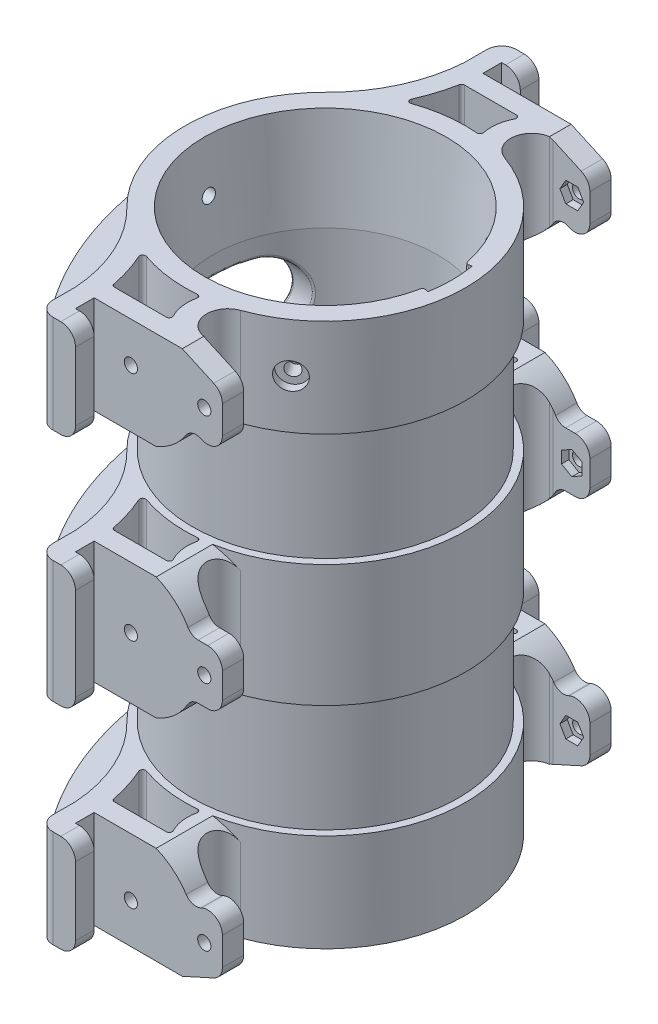
SolidWorks part; units mm, degrees
ref_plane "Front Plane" through (0, 0, 0) normal (0, 0, 1) x (1, 0, 0)
ref_plane "Top Plane" through (0, 0, 0) normal (0, 1, 0) x (1, 0, 0)
ref_plane "Right Plane" through (0, 0, 0) normal (1, 0, 0) x (0, 0, -1)
sketch "Sketch1" plane through (0, 0, 0) normal (0, 1, 0) x (1, 0, 0)
  line L0 (0, 38.25) -> (0, 45.25) construction
  circle A0 centre (0, 0) radius 38.25
  circle A1 centre (0, 0) radius 45.25
  dimension "D1" = 76.5
  dimension "D2" = 7
extrude "Boss-Extrude1" add sketch "Sketch1" along normal mid plane 185
sketch "Sketch2" plane through (0, -92.5, 0) normal (0, -1, 0) x (1, 0, 0)
  line L0 (0, 36.25) -> (0, 38.25) construction
  circle A0 centre (0, 0) radius 36.25
  circle A1 centre (0, 0) radius 38.25 construction
  circle A2 centre (0, 0) radius 38.25
  dimension "D1" = 2
extrude "Boss-Extrude2" add sketch "Sketch2" against normal blind 100 from offset 6.35 offset against normal yes
sketch "Sketch7" plane through (0, 0, 0) normal (1, 0, 0) x (0, 0, -1)
  line L0 (45.25, 92.5) -> (-45.25, 92.5) construction
  line L1 (12.5, 40) -> (-12.5, 40) construction
  line L2 (12.5, 27.5) -> (-12.5, 27.5)
  line L3 (12.5, 52.5) -> (-12.5, 52.5)
  circle A0 centre (0, 40) radius 12.5 construction
  arc A1 (12.5, 27.5) -> (12.5, 52.5) centre (12.5, 40) ccw
  arc A2 (-12.5, 52.5) -> (-12.5, 27.5) centre (-12.5, 40) ccw
  point P7 (0, 40)
  dimension "D2" = 25
  dimension "D3" = 25
  dimension "D1" = 52.5
extrude "Cut-Extrude4" cut sketch "Sketch7" against normal through all
sketch "Sketch8" plane through (0, 0, 0) normal (0, 1, 0) x (1, 0, 0)
  line L1 (17.5, -66.175) -> (128.1882, -66.175) construction
  line L2 (-18.85, -66.175) -> (-18.85, -78.875)
  line L3 (-18.85, -78.875) -> (-6.15, -78.875)
  line L4 (45.25, 0) -> (-45.25, 0) construction
  line L5 (31.75, 0) -> (50, 0) construction
  line L6 (-6.15, -78.875) -> (-6.15, -72.525)
  line L7 (-12.5, -72.525) -> (17.5, -72.525) construction
  line L8 (-6.15, -72.525) -> (-12.5, -72.525)
  line L9 (-12.5, -72.525) -> (-12.5, -66.175)
  line L10 (-12.5, -66.175) -> (43.65, -66.175)
  line L11 (-12.5, 66.175) -> (43.65, 66.175)
  line L12 (-12.5, 72.525) -> (-12.5, 66.175)
  line L13 (-6.15, 72.525) -> (-12.5, 72.525)
  line L14 (-6.15, 78.875) -> (-6.15, 72.525)
  line L15 (-18.85, 78.875) -> (-6.15, 78.875)
  line L16 (-18.85, 66.175) -> (-18.85, 78.875)
  line L18 (43.65, -66.175) -> (43.65, -58.9107)
  line L19 (43.65, -58.9107) -> (18.65, -58.9107)
  line L20 (43.65, 58.9107) -> (18.65, 58.9107)
  line L21 (43.65, 66.175) -> (43.65, 58.9107)
  line L22 (-12.5, -72.525) -> (-18.85, -72.525) construction
  arc A0 (-32.8241, -31.1471) -> (-18.85, -66.175) centre (-69.7381, -66.175) cw
  circle A1 centre (0, 0) radius 45.25 construction
  arc A2 (-32.8241, -31.1471) -> (15.7007, -42.4388) centre (0, 0) ccw
  arc A3 (-32.8241, 31.1471) -> (15.7007, 42.4388) centre (0, 0) cw
  arc A4 (-32.8241, 31.1471) -> (-18.85, 66.175) centre (-69.7381, 66.175) ccw
  arc A9 (18.65, -58.9107) -> (15.7007, -42.4388) centre (18.65, -50.4107) cw
  arc A10 (18.65, 58.9107) -> (15.7007, 42.4388) centre (18.65, 50.4107) ccw
  dimension "D1" = 8.5
  dimension "D2" = 62.5
  dimension "D3" = 25
extrude "Boss-Extrude3" add sketch "Sketch8" along normal up to surface and the other way up to surface up to face at (0, 92.5, 45.25) other way up to face at (0, -92.5, 45.25)
sketch "Sketch10" plane through (0, 0, 66.175) normal (0, 0, 1) x (1, 0, 0)
  line L0 (17.5, -92.5) -> (43.65, -92.5)
  line L1 (43.65, -92.5) -> (43.65, -80.6536)
  line L2 (-6.15, -59.2129) -> (-32.8241, -59.2129)
  line L3 (128.1882, -42.3564) -> (17.5, -92.5) construction
  line L4 (43.65, -80.6536) -> (17.5, -92.5)
  line L5 (43.65, 80.6536) -> (43.65, 92.5)
  line L6 (17.5, 92.5) -> (128.1882, 42.3564) construction
  line L7 (43.65, 92.5) -> (17.5, 92.5)
  line L8 (-12.5, 92.5) -> (43.65, 92.5) construction
  line L9 (17.5, 92.5) -> (43.65, 80.6536)
  line L10 (43.65, -60.1882) -> (43.65, -9.3209)
  line L11 (79.953, -43.7423) -> (23.8431, -69.161) construction
  line L12 (22.9086, -9.3209) -> (60.2886, -9.3209) construction
  line L21 (22.9086, -9.3209) -> (43.65, -9.3209)
  line L23 (43.65, -60.1882) -> (23.8431, -69.161)
  line L25 (-6.15, 92.5) -> (-6.15, -92.5) construction
  line L26 (-32.8241, 92.5) -> (-32.8241, -92.5) construction
  line L32 (-32.8241, -59.2129) -> (-32.8241, -20.7871)
  line L36 (-32.8241, -20.7871) -> (-6.15, -20.7871)
  line L40 (0, 0) -> (-32.8241, 0) construction
  line L45 (8.611, -59.2129) -> (-6.15, -59.2129)
  line L46 (8.611, -20.7871) -> (-6.15, -20.7871)
  line L47 (-32.8241, 59.2129) -> (-32.8241, 20.7871)
  line L48 (-6.15, 59.2129) -> (-32.8241, 59.2129)
  line L49 (8.611, 59.2129) -> (-6.15, 59.2129)
  line L50 (43.65, 60.1882) -> (23.8431, 69.161)
  line L51 (43.65, 60.1882) -> (43.65, 9.3209)
  line L52 (22.9086, 9.3209) -> (43.65, 9.3209)
  line L53 (8.611, 20.7871) -> (-6.15, 20.7871)
  line L54 (-32.8241, 20.7871) -> (-6.15, 20.7871)
  line L55 (43.65, 92.5) -> (43.65, -92.5) construction
  arc A6 (18.8427, -67.7035) -> (23.8431, -69.161) centre (22.1925, -65.5175) ccw construction
  arc A7 (18.8427, -67.7035) -> (8.611, -59.2129) centre (0, -80) ccw construction
  arc A10 (8.611, -20.7871) -> (19.4507, -11.3102) centre (0, 0) ccw construction
  arc A11 (22.9086, -9.3209) -> (19.4507, -11.3102) centre (22.9086, -13.3209) ccw construction
  arc A18 (18.8427, -67.7035) -> (23.8431, -69.161) centre (22.1925, -65.5175) ccw
  arc A19 (18.8427, -67.7035) -> (8.611, -59.2129) centre (0, -80) ccw
  arc A22 (8.611, -20.7871) -> (19.4507, -11.3102) centre (0, 0) ccw
  arc A23 (22.9086, -9.3209) -> (19.4507, -11.3102) centre (22.9086, -13.3209) ccw
  arc A24 (18.8427, 67.7035) -> (8.611, 59.2129) centre (0, 80) cw
  arc A25 (18.8427, 67.7035) -> (23.8431, 69.161) centre (22.1925, 65.5175) cw
  arc A26 (22.9086, 9.3209) -> (19.4507, 11.3102) centre (22.9086, 13.3209) cw
  arc A27 (8.611, 20.7871) -> (19.4507, 11.3102) centre (0, 0) cw
extrude "Cut-Extrude6" cut sketch "Sketch10" against normal up to surface and the other way through all up to face at (-41.5057, 40, 0)
sketch "Sketch11" plane through (0, 0, -78.875) normal (0, 0, -1) x (-1, 0, 0)
  line L3 (-43.65, 92.5) -> (-43.65, 80.6536)
  line L4 (-17.5, 92.5) -> (-43.65, 92.5)
  line L5 (-43.65, 80.6536) -> (-17.5, 92.5)
  line L6 (-43.65, 92.5) -> (-43.65, 80.6536)
  line L7 (-17.5, 92.5) -> (-43.65, 92.5)
  line L8 (-43.65, 80.6536) -> (-17.5, 92.5)
  line L9 (-43.65, -92.5) -> (-17.5, -92.5)
  line L10 (-43.65, -80.6536) -> (-43.65, -92.5)
  line L11 (-17.5, -92.5) -> (-43.65, -80.6536)
  line L12 (-43.65, -92.5) -> (-17.5, -92.5)
  line L13 (-43.65, -80.6536) -> (-43.65, -92.5)
  line L14 (-17.5, -92.5) -> (-43.65, -80.6536)
  line L20 (32.8241, 20.7871) -> (32.8241, 59.2129)
  line L21 (6.15, 20.7871) -> (32.8241, 20.7871)
  line L22 (-8.611, 20.7871) -> (6.15, 20.7871)
  line L23 (-43.65, 9.3209) -> (-22.9086, 9.3209)
  line L24 (-43.65, 60.1882) -> (-43.65, 9.3209)
  line L25 (-23.8431, 69.161) -> (-43.65, 60.1882)
  line L26 (6.15, 59.2129) -> (-8.611, 59.2129)
  line L27 (32.8241, 59.2129) -> (6.15, 59.2129)
  line L28 (32.8241, 20.7871) -> (32.8241, 59.2129)
  line L29 (6.15, 20.7871) -> (32.8241, 20.7871)
  line L30 (-8.611, 20.7871) -> (6.15, 20.7871)
  line L31 (-43.65, 9.3209) -> (-22.9086, 9.3209)
  line L32 (-43.65, 60.1882) -> (-43.65, 9.3209)
  line L33 (-23.8431, 69.161) -> (-43.65, 60.1882)
  line L34 (6.15, 59.2129) -> (-8.611, 59.2129)
  line L35 (32.8241, 59.2129) -> (6.15, 59.2129)
  line L36 (-22.9086, -9.3209) -> (-43.65, -9.3209)
  line L37 (-43.65, -9.3209) -> (-43.65, -60.1882)
  line L38 (-43.65, -60.1882) -> (-23.8431, -69.161)
  line L39 (-8.611, -59.2129) -> (6.15, -59.2129)
  line L40 (6.15, -59.2129) -> (32.8241, -59.2129)
  line L41 (32.8241, -59.2129) -> (32.8241, -20.7871)
  line L42 (32.8241, -20.7871) -> (6.15, -20.7871)
  line L43 (6.15, -20.7871) -> (-8.611, -20.7871)
  line L44 (-22.9086, -9.3209) -> (-43.65, -9.3209)
  line L45 (-43.65, -9.3209) -> (-43.65, -60.1882)
  line L46 (-43.65, -60.1882) -> (-23.8431, -69.161)
  line L47 (-8.611, -59.2129) -> (6.15, -59.2129)
  line L48 (6.15, -59.2129) -> (32.8241, -59.2129)
  line L49 (32.8241, -59.2129) -> (32.8241, -20.7871)
  line L50 (32.8241, -20.7871) -> (6.15, -20.7871)
  line L51 (6.15, -20.7871) -> (-8.611, -20.7871)
  arc A4 (-8.611, 20.7871) -> (-19.4507, 11.3102) centre (0, 0) ccw
  arc A5 (-22.9086, 9.3209) -> (-19.4507, 11.3102) centre (-22.9086, 13.3209) ccw
  arc A6 (-18.8427, 67.7035) -> (-23.8431, 69.161) centre (-22.1925, 65.5175) ccw
  arc A7 (-18.8427, 67.7035) -> (-8.611, 59.2129) centre (0, 80) ccw
  arc A8 (-8.611, 20.7871) -> (-19.4507, 11.3102) centre (0, 0) ccw
  arc A9 (-22.9086, 9.3209) -> (-19.4507, 11.3102) centre (-22.9086, 13.3209) ccw
  arc A10 (-18.8427, 67.7035) -> (-23.8431, 69.161) centre (-22.1925, 65.5175) ccw
  arc A11 (-18.8427, 67.7035) -> (-8.611, 59.2129) centre (0, 80) ccw
  arc A12 (-23.8431, -69.161) -> (-18.8427, -67.7035) centre (-22.1925, -65.5175) ccw
  arc A13 (-8.611, -59.2129) -> (-18.8427, -67.7035) centre (0, -80) ccw
  arc A14 (-19.4507, -11.3102) -> (-8.611, -20.7871) centre (0, 0) ccw
  arc A15 (-19.4507, -11.3102) -> (-22.9086, -9.3209) centre (-22.9086, -13.3209) ccw
  arc A16 (-23.8431, -69.161) -> (-18.8427, -67.7035) centre (-22.1925, -65.5175) ccw
  arc A17 (-8.611, -59.2129) -> (-18.8427, -67.7035) centre (0, -80) ccw
  arc A18 (-19.4507, -11.3102) -> (-8.611, -20.7871) centre (0, 0) ccw
  arc A19 (-19.4507, -11.3102) -> (-22.9086, -9.3209) centre (-22.9086, -13.3209) ccw
  dimension "D1" = 0
  dimension "D2" = 0
  dimension "D3" = 0
  dimension "D4" = 0
extrude "Cut-Extrude7" cut sketch "Sketch11" against normal up to surface (66.9486 mm away) up to face at (-3.9052, 0.3336, 17.6166)
fillet "Fillet5" radius 5 6 edges at (-18.85, -75.8565, -78.875) (-18.85, 0, -78.875) (-18.85, 75.8565, -78.875) (-18.85, 0, 78.875) (-18.85, -75.8565, 78.875) (-18.85, 75.8565, 78.875)
sketch "Sketch14" plane through (0, 0, -66.175) normal (0, 0, -1) x (-1, 0, 0)
  line L0 (0, 0) -> (-25, 0) construction
  line L5 (-25, 78.8696) -> (-25, 0) construction
  circle A3 centre (-25, 78.8696) radius 2.25
  circle A5 centre (-25, 0) radius 2.25
  circle A7 centre (-25, -78.8696) radius 2.25
  circle A8 centre (0, 0) radius 2.25
  circle A9 centre (0, 78.8696) radius 2.25
  circle A10 centre (0, -78.8696) radius 2.25
  dimension "D1" = 25
  dimension "D2" = 78.8696
  dimension "D3" = 4.5
extrude "Cut-Extrude8" cut sketch "Sketch14" against normal up to surface (7.2643 mm away) up to face at (27.8361, -73.0039, -58.9107)
sketch "Sketch15" plane through (0, 0, 66.175) normal (0, 0, 1) x (1, 0, 0)
  circle A1 centre (0, -78.8696) radius 2.25
  circle A3 centre (0, -78.8696) radius 2.25
  circle A5 centre (0, 78.8696) radius 2.25
  circle A7 centre (0, 78.8696) radius 2.25
  circle A9 centre (0, 0) radius 2.25
  circle A11 centre (0, 0) radius 2.25
  circle A13 centre (25, 78.8696) radius 2.25
  circle A14 centre (25, 78.8696) radius 2.25
  circle A15 centre (25, -78.8696) radius 2.25
  circle A16 centre (25, -78.8696) radius 2.25
  circle A17 centre (25, 0) radius 2.25
  circle A18 centre (25, 0) radius 2.25
  dimension "D1" = 0
  dimension "D2" = 0
  dimension "D3" = 0
  dimension "D4" = 0
  dimension "D5" = 0
  dimension "D6" = 0
extrude "Cut-Extrude9" cut sketch "Sketch15" against normal up to surface (7.2643 mm away) up to face at (27.8361, -73.0039, 58.9107)
sketch "Sketch16" plane through (0, 92.5, 0) normal (0, 1, 0) x (1, 0, 0)
  line L0 (-45.25, 0) -> (-47.75, 0) construction
  circle A0 centre (0, 0) radius 47.75
  circle A1 centre (0, 0) radius 45.25
  arc A2 (-32.8241, 31.1471) -> (-32.8241, -31.1471) centre (0, 0) ccw construction
  dimension "D1" = 2.5
extrude "Boss-Extrude4" add sketch "Sketch16" against normal up to surface (33.2871 mm away) up to face at (-10.3824, 59.2129, 65.577)
sketch "Sketch17" plane through (0, -92.5, 0) normal (0, -1, 0) x (1, 0, 0)
  circle A1 centre (0, 0) radius 45.25
  circle A2 centre (0, 0) radius 45.25
  circle A3 centre (0, 0) radius 47.75
  circle A4 centre (0, 0) radius 47.75
  dimension "D1" = 0
  dimension "D2" = 0
extrude "Boss-Extrude5" add sketch "Sketch17" against normal up to surface (33.2871 mm away) up to face at (-10.3824, -59.2129, 65.577)
sketch "Sketch18" plane through (0, -20.7871, 0) normal (0, -1, 0) x (1, 0, 0)
  circle A1 centre (0, 0) radius 47.75
  circle A2 centre (0, 0) radius 47.75
  circle A3 centre (0, 0) radius 45.25
  circle A4 centre (0, 0) radius 45.25
  dimension "D1" = 0
  dimension "D2" = 0
extrude "Boss-Extrude6" add sketch "Sketch18" against normal up to surface (41.5741 mm away) up to face at (-10.3824, 20.7871, 65.577)
sketch "Sketch20" plane through (0, 0, 0) normal (1, 0, 0) x (0, 0, -1)
  line L0 (-45.25, -20.7871) -> (45.25, -20.7871) construction
  line L1 (46.9672, -59.2129) -> (-46.9672, -59.2129) construction
  line L2 (-45.25, 59.2129) -> (45.25, 59.2129) construction
  line L3 (46.9672, 20.7871) -> (-46.9672, 20.7871) construction
  line L4 (-45.25, -20.7871) -> (45.25, -20.7871) construction
  line L5 (46.9672, -59.2129) -> (-46.9672, -59.2129) construction
  line L6 (-45.25, 59.2129) -> (45.25, 59.2129) construction
  line L7 (46.9672, 20.7871) -> (-46.9672, 20.7871) construction
  line L8 (0, -20.7871) -> (0, -59.2129) construction
  line L9 (0, 59.2129) -> (0, 20.7871) construction
  line L10 (-10, 40) -> (10, 40) construction
  line L11 (-10, 45) -> (10, 45)
  line L12 (-10, 35) -> (10, 35)
  line L13 (0, 0) -> (46.4328, 0) construction
  line L14 (46.4328, 19.5496) -> (46.4328, -19.5496) construction
  line L15 (-10, -40) -> (10, -40) construction
  line L16 (-10, -45) -> (10, -45)
  line L17 (-10, -35) -> (10, -35)
  arc A2 (-10, 45) -> (-10, 35) centre (-10, 40) ccw
  arc A3 (10, 35) -> (10, 45) centre (10, 40) ccw
  arc A4 (-10, -45) -> (-10, -35) centre (-10, -40) cw
  arc A5 (10, -35) -> (10, -45) centre (10, -40) cw
  point P2 (0, 40)
  point P14 (0, -20.7871)
  point P30 (0, -40)
  dimension "D1" = 20
  dimension "D2" = 5
extrude "Cut-Extrude10" [suppressed] cut sketch "Sketch20" along normal through all
pattern_circular "CirPattern1" [suppressed] count 6 over 360 reverse direction yes of bodies 118
ref_plane "Plane1" through (-26.1107, -92.5, 39.9787) normal (0, -1, 0) x (-1, 0, 0)
sketch "Sketch23" plane through (0, -92.5, 0) normal (0, -1, 0) x (1, 0, 0)
  line L0 (0, 0) -> (-47.75, 0) construction
  arc A0 (-18.85, 66.175) -> (-33.5786, 33.9491) centre (-68.7395, 69.4978) cw
  arc A1 (-26.1107, 39.9787) -> (-26.1107, -39.9787) centre (0, 0) ccw construction
  arc A2 (-33.5786, 33.9491) -> (-26.1107, 39.9787) centre (0, 0) cw
  arc A3 (-18.85, 66.175) -> (-26.1107, 39.9787) centre (-69.7381, 66.175) cw
  arc A4 (-18.85, -66.175) -> (-26.1107, -39.9787) centre (-69.7381, -66.175) ccw
  arc A5 (-33.5786, -33.9491) -> (-26.1107, -39.9787) centre (0, 0) ccw
  arc A6 (-18.85, -66.175) -> (-33.5786, -33.9491) centre (-68.7395, -69.4978) ccw
  arc A7 (-26.1107, 39.9787) -> (-18.85, 66.175) centre (-69.7381, 66.175) ccw construction
  dimension "D1" = 50
extrude "Boss-Extrude7" add sketch "Sketch23" against normal up to surface (33.2871 mm away) up to face at (-8.8243, -59.2129, 0)
sketch "Sketch24" plane through (0, 92.5, 0) normal (0, 1, 0) x (1, 0, 0)
  arc A3 (-26.1107, 39.9787) -> (-18.85, 66.175) centre (-69.7381, 66.175) ccw
  arc A4 (-26.1107, 39.9787) -> (-33.5786, 33.9491) centre (0, 0) ccw
  arc A5 (-33.5786, 33.9491) -> (-18.85, 66.175) centre (-68.7395, 69.4978) ccw
  arc A6 (-26.1107, 39.9787) -> (-18.85, 66.175) centre (-69.7381, 66.175) ccw
  arc A7 (-26.1107, 39.9787) -> (-33.5786, 33.9491) centre (0, 0) ccw
  arc A8 (-33.5786, 33.9491) -> (-18.85, 66.175) centre (-68.7395, 69.4978) ccw
  arc A9 (-18.85, -66.175) -> (-33.5786, -33.9491) centre (-68.7395, -69.4978) ccw
  arc A10 (-33.5786, -33.9491) -> (-26.1107, -39.9787) centre (0, 0) ccw
  arc A11 (-18.85, -66.175) -> (-26.1107, -39.9787) centre (-69.7381, -66.175) ccw
  arc A12 (-18.85, -66.175) -> (-33.5786, -33.9491) centre (-68.7395, -69.4978) ccw
  arc A13 (-33.5786, -33.9491) -> (-26.1107, -39.9787) centre (0, 0) ccw
  arc A14 (-18.85, -66.175) -> (-26.1107, -39.9787) centre (-69.7381, -66.175) ccw
  dimension "D1" = 0
  dimension "D2" = 0
extrude "Boss-Extrude8" add sketch "Sketch24" against normal up to surface (33.2871 mm away) up to face at (-45.25, 59.2129, 0)
sketch "Sketch25" plane through (0, 20.7871, 0) normal (0, 1, 0) x (1, 0, 0)
  arc A3 (-18.85, -66.175) -> (-33.5786, -33.9491) centre (-68.7395, -69.4978) ccw
  arc A4 (-33.5786, -33.9491) -> (-26.1107, -39.9787) centre (0, 0) ccw
  arc A5 (-18.85, -66.175) -> (-26.1107, -39.9787) centre (-69.7381, -66.175) ccw
  arc A6 (-18.85, -66.175) -> (-33.5786, -33.9491) centre (-68.7395, -69.4978) ccw
  arc A7 (-33.5786, -33.9491) -> (-26.1107, -39.9787) centre (0, 0) ccw
  arc A8 (-18.85, -66.175) -> (-26.1107, -39.9787) centre (-69.7381, -66.175) ccw
  arc A9 (-26.1107, 39.9787) -> (-18.85, 66.175) centre (-69.7381, 66.175) ccw
  arc A10 (-33.5786, 33.9491) -> (-18.85, 66.175) centre (-68.7395, 69.4978) ccw
  arc A11 (-26.1107, 39.9787) -> (-33.5786, 33.9491) centre (0, 0) ccw
  arc A12 (-26.1107, 39.9787) -> (-18.85, 66.175) centre (-69.7381, 66.175) ccw
  arc A13 (-33.5786, 33.9491) -> (-18.85, 66.175) centre (-68.7395, 69.4978) ccw
  arc A14 (-26.1107, 39.9787) -> (-33.5786, 33.9491) centre (0, 0) ccw
  dimension "D1" = 0
  dimension "D2" = 0
extrude "Boss-Extrude9" add sketch "Sketch25" against normal up to surface (41.5741 mm away) up to face at (-45.25, -20.7871, 0)
sketch "Sketch27" plane through (0, 0, 0) normal (0, 0, 1) x (1, 0, 0)
  line L0 (38.25, 59.2129) -> (41.1622, 92.5)
  line L3 (38.25, 59.2129) -> (0, 59.2129) construction
  line L5 (-18.85, 92.5) -> (-33.5786, 92.5) construction
  line L6 (38.25, 59.2129) -> (38.25, 92.5)
  line L7 (38.25, 92.5) -> (41.1622, 92.5)
  line L8 (0, 59.2129) -> (0, 92.5) construction
  dimension "D1" = 33.2871
  dimension "D2" = 5
  dimension "D3" = 38.25
  dimension "D4" = 38.25
  dimension "D5" = 38.25
revolve "Cut-Revolve1" cut sketch "Sketch27" angle 360 about L8
sketch "Sketch28" plane through (0, 92.5, 0) normal (0, 1, 0) x (1, 0, 0)
  line L1 (43.65, 58.9107) -> (18.65, 58.9107) construction
  line L2 (0, 0) -> (47.75, 0) construction
  line L3 (11.1383, 46.4328) -> (10.15, 46.6698)
  line L4 (10.15, 46.6698) -> (10.15, 58.8326)
  line L5 (10.15, 58.8326) -> (17.5, 58.8326)
  line L6 (10.15, -58.8326) -> (17.5, -58.8326)
  line L7 (10.15, -46.6698) -> (10.15, -58.8326)
  line L8 (11.1383, -46.4328) -> (10.15, -46.6698)
  arc A0 (17.5, 58.8326) -> (16.1276, 44.944) centre (18.5576, 51.716) ccw
  arc A1 (11.1383, -46.4328) -> (11.1383, 46.4328) centre (0, 0) ccw construction
  arc A2 (16.1276, 44.944) -> (11.1383, 46.4328) centre (0, 0) ccw
  arc A7 (17.5, 58.8326) -> (11.1383, 46.4328) centre (18.65, 50.4107) ccw construction
  arc A8 (16.1276, -44.944) -> (11.1383, -46.4328) centre (0, 0) cw
  arc A9 (17.5, -58.8326) -> (16.1276, -44.944) centre (18.5576, -51.716) cw
extrude "Boss-Extrude13" add sketch "Sketch28" against normal up to surface (26.6421 mm away) up to face at (13.4579, 62.8457, 57.713)
sketch "Sketch29" plane through (0, -92.5, 0) normal (0, -1, 0) x (1, 0, 0)
  line L3 (11.1383, -46.4328) -> (10.15, -46.6698)
  line L4 (10.15, -46.6698) -> (10.15, -58.8326)
  line L5 (10.15, -58.8326) -> (17.5, -58.8326)
  line L6 (11.1383, -46.4328) -> (10.15, -46.6698)
  line L7 (10.15, -46.6698) -> (10.15, -58.8326)
  line L8 (10.15, -58.8326) -> (17.5, -58.8326)
  line L9 (17.5, 58.8326) -> (10.15, 58.8326)
  line L10 (10.15, 46.6698) -> (11.1383, 46.4328)
  line L11 (10.15, 58.8326) -> (10.15, 46.6698)
  line L12 (17.5, 58.8326) -> (10.15, 58.8326)
  line L13 (10.15, 46.6698) -> (11.1383, 46.4328)
  line L14 (10.15, 58.8326) -> (10.15, 46.6698)
  arc A2 (16.1276, -44.944) -> (17.5, -58.8326) centre (18.5576, -51.716) ccw
  arc A3 (11.1383, -46.4328) -> (16.1276, -44.944) centre (0, 0) ccw
  arc A4 (16.1276, -44.944) -> (17.5, -58.8326) centre (18.5576, -51.716) ccw
  arc A5 (11.1383, -46.4328) -> (16.1276, -44.944) centre (0, 0) ccw
  arc A6 (17.5, 58.8326) -> (16.1276, 44.944) centre (18.5576, 51.716) ccw
  arc A7 (16.1276, 44.944) -> (11.1383, 46.4328) centre (0, 0) ccw
  arc A8 (17.5, 58.8326) -> (16.1276, 44.944) centre (18.5576, 51.716) ccw
  arc A9 (16.1276, 44.944) -> (11.1383, 46.4328) centre (0, 0) ccw
  dimension "D1" = 0
  dimension "D2" = 0
extrude "Boss-Extrude14" add sketch "Sketch29" against normal up to surface (32.0496 mm away) up to face at (13.7418, -62.9735, 57.3608)
sketch "Sketch30" plane through (0, 0, 0) normal (0, 1, 0) x (1, 0, 0)
  line L3 (10.15, 46.6698) -> (11.1383, 46.4328)
  line L4 (10.15, 58.8326) -> (10.15, 46.6698)
  line L5 (17.5, 58.8326) -> (10.15, 58.8326)
  line L6 (10.15, 46.6698) -> (11.1383, 46.4328)
  line L7 (10.15, 58.8326) -> (10.15, 46.6698)
  line L8 (17.5, 58.8326) -> (10.15, 58.8326)
  line L9 (10.15, -46.6698) -> (10.15, -58.8326)
  line L10 (10.15, -58.8326) -> (17.5, -58.8326)
  line L11 (11.1383, -46.4328) -> (10.15, -46.6698)
  line L12 (10.15, -46.6698) -> (10.15, -58.8326)
  line L13 (10.15, -58.8326) -> (17.5, -58.8326)
  line L14 (11.1383, -46.4328) -> (10.15, -46.6698)
  arc A2 (17.5, 58.8326) -> (16.1276, 44.944) centre (18.5576, 51.716) ccw
  arc A3 (16.1276, 44.944) -> (11.1383, 46.4328) centre (0, 0) ccw
  arc A4 (17.5, 58.8326) -> (16.1276, 44.944) centre (18.5576, 51.716) ccw
  arc A5 (16.1276, 44.944) -> (11.1383, 46.4328) centre (0, 0) ccw
  arc A6 (16.1276, -44.944) -> (17.5, -58.8326) centre (18.5576, -51.716) ccw
  arc A7 (11.1383, -46.4328) -> (16.1276, -44.944) centre (0, 0) ccw
  arc A8 (16.1276, -44.944) -> (17.5, -58.8326) centre (18.5576, -51.716) ccw
  arc A9 (11.1383, -46.4328) -> (16.1276, -44.944) centre (0, 0) ccw
  dimension "D1" = 0
  dimension "D2" = 0
extrude "Boss-Extrude15" add sketch "Sketch30" against normal up to surface and the other way up to surface up to face at (13.9691, -16.7184, -57.3608) other way up to face at (13.6851, 16.8462, -57.713)
ref_plane "Plane2" through (0, 75.8565, 0) normal (0, 1, 0) x (1, 0, 0)
sketch "Sketch31" plane through (0, 75.8565, 0) normal (0, 1, 0) x (1, 0, 0)
  line L0 (0, 0) -> (27.3883, 39.1145) construction
  line L1 (0, 0) -> (-47.75, 0) construction
  arc A0 (16.1276, -44.944) -> (16.1276, 44.944) centre (0, 0) ccw construction
  arc A1 (-33.5786, 33.9491) -> (-33.5786, -33.9491) centre (0, 0) ccw construction
  dimension "D1" = 125
ref_plane "Plane3" through (27.3883, 75.8565, -39.1145) normal (0.5736, 0, -0.8192) x (-0.8192, 0, -0.5736)
sketch "Sketch34" plane through (0, 75.8565, 0) normal (0, 1, 0) x (1, 0, 0)
  line L2 (0, 0) -> (-47.76, 0) construction
  line L5 (-18.85, 73.875) -> (-18.85, 66.175) construction
  line L6 (-18.85, 73.875) -> (-18.85, 66.175)
  line L7 (-18.85, -73.875) -> (-18.85, -66.175)
  arc A1 (-17.5219, 77.2686) -> (-17.5219, -77.2686) centre (66.083, 0) ccw
  arc A9 (-13.85, 78.875) -> (-18.85, 73.875) centre (-13.85, 73.875) ccw construction
  arc A17 (-18.85, -73.875) -> (-13.85, -78.875) centre (-13.85, -73.875) ccw construction
  arc A18 (-17.5219, 77.2686) -> (-18.85, 73.875) centre (-13.85, 73.875) ccw
  arc A19 (-33.5786, 33.9491) -> (-33.5786, -33.9491) centre (0, 0) ccw construction
  arc A20 (-33.5786, 33.9491) -> (-18.85, 66.175) centre (-68.7395, 69.4978) ccw construction
  arc A21 (-33.5786, 33.9491) -> (-33.5786, -33.9491) centre (0, 0) ccw
  arc A22 (-33.5786, 33.9491) -> (-18.85, 66.175) centre (-68.7395, 69.4978) ccw
  arc A23 (-33.5786, -33.9491) -> (-18.85, -66.175) centre (-68.7395, -69.4978) cw
  arc A24 (-17.5219, -77.2686) -> (-18.85, -73.875) centre (-13.85, -73.875) cw
  point P24 (-47.75, 0)
  dimension "D1" = 0.01
extrude "Boss-Extrude17" add sketch "Sketch34" along normal mid plane 15
ref_plane "Plane4" through (0, 0, 0) normal (0, -1, 0) x (-1, 0, 0)
ref_plane "Plane5" through (0, -75.8565, 0) normal (0, -1, 0) x (-1, 0, 0)
sketch "Sketch35" plane through (0, 0, 0) normal (0, -1, 0) x (-1, 0, 0)
  line L3 (18.85, -66.175) -> (18.85, -73.875)
  line L5 (18.85, 73.875) -> (18.85, 66.175)
  line L6 (18.85, -66.175) -> (18.85, -73.875)
  line L7 (18.85, 73.875) -> (18.85, 66.175)
  arc A12 (18.85, 66.175) -> (33.5786, 33.9491) centre (68.7395, 69.4978) ccw
  arc A13 (33.5786, -33.9491) -> (33.5786, 33.9491) centre (0, 0) ccw
  arc A20 (33.5786, -33.9491) -> (18.85, -66.175) centre (68.7395, -69.4978) ccw
  arc A21 (17.5219, -77.2686) -> (18.85, -73.875) centre (13.85, -73.875) ccw
  arc A25 (17.5219, -77.2686) -> (17.5219, 77.2686) centre (-66.083, 0) ccw
  arc A38 (18.85, 73.875) -> (17.5219, 77.2686) centre (13.85, 73.875) ccw
  arc A39 (18.85, 66.175) -> (33.5786, 33.9491) centre (68.7395, 69.4978) ccw
  arc A40 (33.5786, -33.9491) -> (33.5786, 33.9491) centre (0, 0) ccw
  arc A41 (33.5786, -33.9491) -> (18.85, -66.175) centre (68.7395, -69.4978) ccw
  arc A42 (17.5219, -77.2686) -> (18.85, -73.875) centre (13.85, -73.875) ccw
  arc A43 (17.5219, -77.2686) -> (17.5219, 77.2686) centre (-66.083, 0) ccw
  arc A44 (18.85, 73.875) -> (17.5219, 77.2686) centre (13.85, 73.875) ccw
  dimension "D1" = 0
extrude "Boss-Extrude18" add sketch "Sketch35" along normal mid plane 19.1435
sketch "Sketch36" plane through (0, -75.8565, 0) normal (0, -1, 0) x (-1, 0, 0)
  line L3 (18.85, 73.875) -> (18.85, 66.175)
  line L5 (18.85, -66.175) -> (18.85, -73.875)
  line L6 (18.85, 73.875) -> (18.85, 66.175)
  line L7 (18.85, -66.175) -> (18.85, -73.875)
  arc A12 (18.85, 66.175) -> (33.5786, 33.9491) centre (68.7395, 69.4978) ccw
  arc A13 (33.5786, -33.9491) -> (33.5786, 33.9491) centre (0, 0) ccw
  arc A20 (33.5786, -33.9491) -> (18.85, -66.175) centre (68.7395, -69.4978) ccw
  arc A21 (17.5219, -77.2686) -> (18.85, -73.875) centre (13.85, -73.875) ccw
  arc A25 (17.5219, -77.2686) -> (17.5219, 77.2686) centre (-66.083, 0) ccw
  arc A38 (18.85, 73.875) -> (17.5219, 77.2686) centre (13.85, 73.875) ccw
  arc A39 (18.85, 66.175) -> (33.5786, 33.9491) centre (68.7395, 69.4978) ccw
  arc A40 (33.5786, -33.9491) -> (33.5786, 33.9491) centre (0, 0) ccw
  arc A41 (33.5786, -33.9491) -> (18.85, -66.175) centre (68.7395, -69.4978) ccw
  arc A42 (17.5219, -77.2686) -> (18.85, -73.875) centre (13.85, -73.875) ccw
  arc A43 (17.5219, -77.2686) -> (17.5219, 77.2686) centre (-66.083, 0) ccw
  arc A44 (18.85, 73.875) -> (17.5219, 77.2686) centre (13.85, 73.875) ccw
  dimension "D1" = 0
extrude "Boss-Extrude19" add sketch "Sketch36" along normal mid plane 15
sketch "Sketch32" plane through (27.3883, 75.8565, -39.1145) normal (0.5736, 0, -0.8192) x (-0.8192, 0, -0.5736)
  circle A0 centre (0, 0) radius 4.5
  dimension "D1" = 9
extrude "Cut-Extrude18" cut sketch "Sketch32" against normal blind 3 and the other way blind 4
sketch "Sketch33" plane through (25.6675, 0, -36.6571) normal (0.5736, 0, -0.8192) x (-0.8192, 0, -0.5736)
  circle A0 centre (0, 75.8565) radius 2.25
  dimension "D1" = 4.5
extrude "Cut-Extrude11" cut sketch "Sketch33" against normal up to surface (5.1077 mm away) up to face at (0, 92.5, -41.1622)
pattern_circular "CirPattern2" count 3 over 250 about axis through (0, 59.2129, 0) along (0, -1, 0) of "Cut-Extrude11", "Cut-Extrude18" reverse direction yes
sketch "Sketch37" plane through (0, 0, 58.9107) normal (0, 0, -1) x (-1, 0, 0)
  line L1 (-2.0207, -3.5) -> (2.0207, -3.5)
  line L2 (2.0207, -3.5) -> (4.0415, 0)
  line L3 (4.0415, 0) -> (2.0207, 3.5)
  line L4 (2.0207, 3.5) -> (-2.0207, 3.5)
  line L5 (-2.0207, 3.5) -> (-4.0415, 0)
  line L6 (-4.0415, 0) -> (-2.0207, -3.5)
  line L13 (-28.5, 2.0207) -> (-28.5, -2.0207)
  line L14 (-28.5, -2.0207) -> (-25, -4.0415)
  line L15 (-25, -4.0415) -> (-21.5, -2.0207)
  line L16 (-21.5, -2.0207) -> (-21.5, 2.0207)
  line L17 (-21.5, 2.0207) -> (-25, 4.0415)
  line L18 (-25, 4.0415) -> (-28.5, 2.0207)
  line L25 (-29.0415, -78.8696) -> (-27.0207, -82.3696)
  line L26 (-27.0207, -82.3696) -> (-22.9793, -82.3696)
  line L27 (-22.9793, -82.3696) -> (-20.9585, -78.8696)
  line L28 (-20.9585, -78.8696) -> (-22.9793, -75.3696)
  line L29 (-22.9793, -75.3696) -> (-27.0207, -75.3696)
  line L30 (-27.0207, -75.3696) -> (-29.0415, -78.8696)
  line L37 (-2.0207, -82.3696) -> (2.0207, -82.3696)
  line L38 (2.0207, -82.3696) -> (4.0415, -78.8696)
  line L39 (4.0415, -78.8696) -> (2.0207, -75.3696)
  line L40 (2.0207, -75.3696) -> (-2.0207, -75.3696)
  line L41 (-2.0207, -75.3696) -> (-4.0415, -78.8696)
  line L42 (-4.0415, -78.8696) -> (-2.0207, -82.3696)
  line L43 (-2.0207, 75.3696) -> (2.0207, 75.3696)
  line L44 (2.0207, 75.3696) -> (4.0415, 78.8696)
  line L45 (4.0415, 78.8696) -> (2.0207, 82.3696)
  line L46 (2.0207, 82.3696) -> (-2.0207, 82.3696)
  line L47 (-2.0207, 82.3696) -> (-4.0415, 78.8696)
  line L48 (-4.0415, 78.8696) -> (-2.0207, 75.3696)
  line L49 (-27.0207, 75.3696) -> (-22.9793, 75.3696)
  line L50 (-22.9793, 75.3696) -> (-20.9585, 78.8696)
  line L51 (-20.9585, 78.8696) -> (-22.9793, 82.3696)
  line L52 (-22.9793, 82.3696) -> (-27.0207, 82.3696)
  line L53 (-27.0207, 82.3696) -> (-29.0415, 78.8696)
  line L54 (-29.0415, 78.8696) -> (-27.0207, 75.3696)
  circle A1 centre (-25, -78.8696) radius 2.25 construction
  circle A3 centre (-25, 0) radius 2.25 construction
  circle A5 centre (0, 0) radius 2.25 construction
  circle A7 centre (-25, -78.8696) radius 2.25 construction
  circle A9 centre (-25, 0) radius 2.25 construction
  circle A11 centre (0, 0) radius 2.25 construction
  circle A12 centre (0, 0) radius 3.5 construction
  circle A13 centre (0, 78.8696) radius 2.25 construction
  circle A14 centre (-25, 0) radius 3.5 construction
  circle A15 centre (-25, 78.8696) radius 2.25 construction
  circle A16 centre (-25, -78.8696) radius 3.5 construction
  circle A17 centre (0, -78.8696) radius 2.25 construction
  circle A18 centre (0, 78.8696) radius 2.25 construction
  circle A19 centre (-25, 78.8696) radius 2.25 construction
  circle A20 centre (0, -78.8696) radius 2.25 construction
  circle A21 centre (0, -78.8696) radius 3.5 construction
  circle A22 centre (0, 78.8696) radius 3.5 construction
  circle A23 centre (-25, 78.8696) radius 3.5 construction
  dimension "D2" = 7
  dimension "D3" = 4.0415
extrude "Cut-Extrude12" cut sketch "Sketch37" against normal blind 2.5
sketch "Sketch39" plane through (0, 0, -58.9107) normal (0, 0, 1) x (1, 0, 0)
  line L78 (-2.0207, -82.3696) -> (2.0207, -82.3696)
  line L79 (-4.0415, -78.8696) -> (-2.0207, -82.3696)
  line L80 (-2.0207, -75.3696) -> (-4.0415, -78.8696)
  line L81 (2.0207, -75.3696) -> (-2.0207, -75.3696)
  line L82 (4.0415, -78.8696) -> (2.0207, -75.3696)
  line L83 (2.0207, -82.3696) -> (4.0415, -78.8696)
  line L84 (-2.0207, -82.3696) -> (2.0207, -82.3696)
  line L85 (-4.0415, -78.8696) -> (-2.0207, -82.3696)
  line L86 (-2.0207, -75.3696) -> (-4.0415, -78.8696)
  line L87 (2.0207, -75.3696) -> (-2.0207, -75.3696)
  line L88 (4.0415, -78.8696) -> (2.0207, -75.3696)
  line L89 (2.0207, -82.3696) -> (4.0415, -78.8696)
  line L90 (-2.0207, -3.5) -> (2.0207, -3.5)
  line L91 (-4.0415, 0) -> (-2.0207, -3.5)
  line L92 (-2.0207, 3.5) -> (-4.0415, 0)
  line L93 (2.0207, 3.5) -> (-2.0207, 3.5)
  line L94 (4.0415, 0) -> (2.0207, 3.5)
  line L95 (2.0207, -3.5) -> (4.0415, 0)
  line L96 (-2.0207, -3.5) -> (2.0207, -3.5)
  line L97 (-4.0415, 0) -> (-2.0207, -3.5)
  line L98 (-2.0207, 3.5) -> (-4.0415, 0)
  line L99 (2.0207, 3.5) -> (-2.0207, 3.5)
  line L100 (4.0415, 0) -> (2.0207, 3.5)
  line L101 (2.0207, -3.5) -> (4.0415, 0)
  line L102 (-2.0207, 75.3696) -> (2.0207, 75.3696)
  line L103 (-4.0415, 78.8696) -> (-2.0207, 75.3696)
  line L104 (-2.0207, 82.3696) -> (-4.0415, 78.8696)
  line L105 (2.0207, 82.3696) -> (-2.0207, 82.3696)
  line L106 (4.0415, 78.8696) -> (2.0207, 82.3696)
  line L107 (2.0207, 75.3696) -> (4.0415, 78.8696)
  line L108 (-2.0207, 75.3696) -> (2.0207, 75.3696)
  line L109 (-4.0415, 78.8696) -> (-2.0207, 75.3696)
  line L110 (-2.0207, 82.3696) -> (-4.0415, 78.8696)
  line L111 (2.0207, 82.3696) -> (-2.0207, 82.3696)
  line L112 (4.0415, 78.8696) -> (2.0207, 82.3696)
  line L113 (2.0207, 75.3696) -> (4.0415, 78.8696)
  line L114 (28.5, -2.0207) -> (28.5, 2.0207)
  line L115 (25, -4.0415) -> (28.5, -2.0207)
  line L116 (21.5, -2.0207) -> (25, -4.0415)
  line L117 (21.5, 2.0207) -> (21.5, -2.0207)
  line L118 (25, 4.0415) -> (21.5, 2.0207)
  line L119 (28.5, 2.0207) -> (25, 4.0415)
  line L120 (28.5, -2.0207) -> (28.5, 2.0207)
  line L121 (25, -4.0415) -> (28.5, -2.0207)
  line L122 (21.5, -2.0207) -> (25, -4.0415)
  line L123 (21.5, 2.0207) -> (21.5, -2.0207)
  line L124 (25, 4.0415) -> (21.5, 2.0207)
  line L125 (28.5, 2.0207) -> (25, 4.0415)
  line L126 (22.9793, 75.3696) -> (27.0207, 75.3696)
  line L127 (20.9585, 78.8696) -> (22.9793, 75.3696)
  line L128 (22.9793, 82.3696) -> (20.9585, 78.8696)
  line L129 (27.0207, 82.3696) -> (22.9793, 82.3696)
  line L130 (29.0415, 78.8696) -> (27.0207, 82.3696)
  line L131 (27.0207, 75.3696) -> (29.0415, 78.8696)
  line L132 (22.9793, 75.3696) -> (27.0207, 75.3696)
  line L133 (20.9585, 78.8696) -> (22.9793, 75.3696)
  line L134 (22.9793, 82.3696) -> (20.9585, 78.8696)
  line L135 (27.0207, 82.3696) -> (22.9793, 82.3696)
  line L136 (29.0415, 78.8696) -> (27.0207, 82.3696)
  line L137 (27.0207, 75.3696) -> (29.0415, 78.8696)
  line L138 (22.9793, -82.3696) -> (27.0207, -82.3696)
  line L139 (20.9585, -78.8696) -> (22.9793, -82.3696)
  line L140 (22.9793, -75.3696) -> (20.9585, -78.8696)
  line L141 (27.0207, -75.3696) -> (22.9793, -75.3696)
  line L142 (29.0415, -78.8696) -> (27.0207, -75.3696)
  line L143 (27.0207, -82.3696) -> (29.0415, -78.8696)
  line L144 (22.9793, -82.3696) -> (27.0207, -82.3696)
  line L145 (20.9585, -78.8696) -> (22.9793, -82.3696)
  line L146 (22.9793, -75.3696) -> (20.9585, -78.8696)
  line L147 (27.0207, -75.3696) -> (22.9793, -75.3696)
  line L148 (29.0415, -78.8696) -> (27.0207, -75.3696)
  line L149 (27.0207, -82.3696) -> (29.0415, -78.8696)
  dimension "D1" = 0
  dimension "D2" = 0
  dimension "D3" = 0
  dimension "D4" = 0
  dimension "D5" = 0
  dimension "D6" = 0
extrude "Cut-Extrude13" cut sketch "Sketch39" against normal blind 2.5
sketch "Sketch44" plane through (0, 0, 0) normal (0, 0, 1) x (1, 0, 0)
  line L0 (41.1622, 92.5) -> (-41.1622, 92.5) construction
  line L1 (41.1622, 92.5) -> (-41.1622, 92.5) construction
  line L2 (41.1622, 92.5) -> (43.1622, 92.5)
  line L3 (38.25, 59.2129) -> (-38.25, 59.2129) construction
  line L4 (38.25, 59.2129) -> (-38.25, 59.2129) construction
  line L5 (38.25, 59.2129) -> (40.25, 59.2129)
  line L6 (40.25, 59.2129) -> (43.1622, 92.5)
  line L7 (38.25, 59.2129) -> (41.1622, 92.5)
  line L8 (0, 59.2129) -> (0, 92.5) construction
  dimension "D1" = 2
revolve "Cut-Revolve2" cut sketch "Sketch44" angle 10 about L8 other way angle 10
fillet "Fillet6" radius 1 2 edges at (39.1029, 75.8565, -6.8949) (39.1029, 75.8565, 6.8949)
sketch "Sketch45" plane through (0, 92.5, 0) normal (0, 1, 0) x (1, 0, 0)
  line L3 (0, 0) -> (47.75, 0) construction
  line L4 (-12.5, 59.5872) -> (7.2438, 59.5872)
  line L5 (-13.0263, 59.5872) -> (7.2438, 59.5872)
  line L6 (-13.0263, -59.5872) -> (7.2438, -59.5872)
  circle A0 centre (0, 0) radius 47.75 construction
  arc A1 (16.1276, -44.944) -> (16.1276, 44.944) centre (0, 0) ccw construction
  arc A2 (5.456, 47.4373) -> (-18.1353, 44.1721) centre (0, 0) ccw
  arc A3 (-18.1353, -44.1721) -> (-13.0263, -59.5872) centre (-68.7395, -69.4978) cw
  arc A4 (5.456, -47.4373) -> (-18.1353, -44.1721) centre (0, 0) cw
  arc A5 (7.2438, -59.5872) -> (5.456, -47.4373) centre (18.5576, -51.716) cw
  arc A6 (-28.946, 29.2653) -> (-12.2768, 65.7372) centre (-68.7395, 69.4978) ccw
  arc A7 (-18.1353, 44.1721) -> (-13.0263, 59.5872) centre (-68.7395, 69.4978) ccw
  arc A9 (7.2438, 59.5872) -> (13.9025, 38.7434) centre (18.5576, 51.716) ccw
  arc A10 (7.2438, 59.5872) -> (5.456, 47.4373) centre (18.5576, 51.716) ccw
  dimension "D1" = 6.5878
  dimension "D2" = 6.5878
extrude "Cut-Extrude14" cut sketch "Sketch45" against normal through all both and the other way through all
fillet "Fillet7" radius 1 24 edges at (5.456, 75.8565, 47.4373) (5.456, 0, 47.4373) (5.456, -75.8565, 47.4373) (7.2438, 75.8565, 59.5872) (-13.0263, 75.8565, 59.5872) (-18.1353, 75.8565, 44.1721) (-18.1353, 0, 44.1721) (-18.1353, -75.8565, 44.1721) (-18.1353, 75.8565, -44.1721) (-18.1353, 0, -44.1721) (-18.1353, -75.8565, -44.1721) (5.456, 0, -47.4373) (5.456, -75.8565, -47.4373) (7.2438, 75.8565, -59.5872) (-13.0263, 75.8565, -59.5872) (5.456, 75.8565, -47.4373)
sketch "Sketch47" plane through (0, 0, 66.175) normal (0, 0, 1) x (1, 0, 0)
  line L0 (31.15, 9.3209) -> (31.15, -9.3209) construction
  line L1 (43.65, 9.3209) -> (22.9086, 9.3209) construction
  line L2 (22.9086, -9.3209) -> (43.65, -9.3209) construction
  line L3 (43.65, 9.3209) -> (43.65, -9.3209) construction
  line L4 (17.5, -92.5) -> (43.65, -80.6536) construction
  line L5 (31.15, -86.3163) -> (43.65, -86.3163)
  line L6 (31.15, -86.3163) -> (31.15, 86.3163)
  line L7 (31.15, 86.3163) -> (43.65, 86.3163)
  line L8 (43.65, -86.3163) -> (43.65, 86.3163)
  line L10 (43.65, 80.6536) -> (17.5, 92.5) construction
  dimension "D1" = 12.5
extrude "Shorten_(editable)" cut sketch "Sketch47" against normal up to surface (7.2643 mm away) up to face at (25, 78.8696, 58.9107)
sketch "Sketch48" plane through (0, 0, -66.175) normal (0, 0, -1) x (-1, 0, 0)
  line L4 (-43.65, -86.3163) -> (-31.15, -86.3163)
  line L5 (-43.65, 86.3163) -> (-43.65, -86.3163)
  line L6 (-31.15, 86.3163) -> (-43.65, 86.3163)
  line L7 (-31.15, -86.3163) -> (-31.15, 86.3163)
  line L8 (-43.65, -86.3163) -> (-31.15, -86.3163)
  line L9 (-43.65, 86.3163) -> (-43.65, -86.3163)
  line L10 (-31.15, 86.3163) -> (-43.65, 86.3163)
  line L11 (-31.15, -86.3163) -> (-31.15, 86.3163)
  dimension "D1" = 0
extrude "Cut-Extrude16" cut sketch "Sketch48" against normal up to surface (7.2643 mm away) up to face at (25, 78.8696, -58.9107)
fillet "Fillet8" radius 5 24 edges at (31.15, 86.3163, -62.5429) (31.15, 65.8509, -62.5429) (31.15, 9.3209, -62.5429) (31.15, -9.3209, -62.5429) (31.15, -65.8509, -62.5429) (31.15, -86.3163, -62.5429) (31.15, -86.3163, 62.5429) (31.15, -65.8509, 62.5429) (31.15, -9.3209, 62.5429) (31.15, 9.3209, 62.5429) (31.15, 86.3163, 62.5429) (31.15, 65.8509, 62.5429) (-6.15, -59.2129, -75.7) (-6.15, -92.5, -75.7) (-6.15, -20.7871, -75.7) (-6.15, 20.7871, -75.7) (-6.15, 59.2129, -75.7) (-6.15, 92.5, -75.7) (-6.15, 92.5, 75.7) (-6.15, 59.2129, 75.7) (-6.15, -20.7871, 75.7) (-6.15, 20.7871, 75.7) (-6.15, -59.2129, 75.7) (-6.15, -92.5, 75.7)
fillet "Fillet9" radius 1 8 edges at (-45.25, 52.5, 0) (-37.7613, 41.2941, -24.9328) (-45.25, 27.5, 0) (-38.25, 52.5, 0) (-28.9895, 41.0782, -24.9534) (-38.25, 27.5, 0) (-37.7613, 38.7059, 24.9328) (-28.9895, 38.9218, 24.9534)
